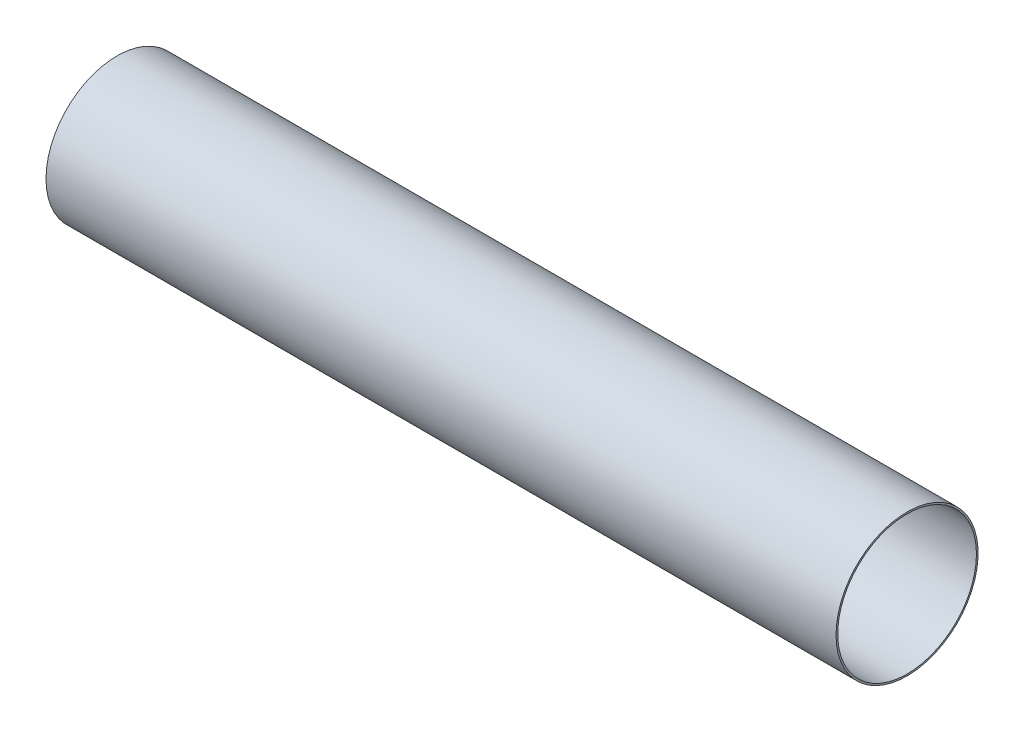
SolidWorks part; units mm, degrees
material "Thornel Mat VMA"
ref_plane "Front Plane" through (0, 0, 0) normal (0, 0, 1) x (1, 0, 0)
ref_plane "Top Plane" through (0, 0, 0) normal (0, 1, 0) x (1, 0, 0)
ref_plane "Right Plane" through (0, 0, 0) normal (1, 0, 0) x (0, 0, -1)
sketch "Sketch1" plane through (0, 0, 0) normal (1, 0, 0) x (0, 0, -1)
  circle A0 centre (0, 0) radius 84.55
  dimension "D1" = 169.1
extrude "Boss-Extrude2" add sketch "Sketch1" along normal blind 940 contours A0
sketch "Sketch3" plane through (940, 0, 0) normal (1, 0, 0) x (0, 0, -1)
  circle A0 centre (0, 0) radius 82.55
  dimension "D1" = 165.1
extrude "Cut-Extrude1" cut sketch "Sketch3" against normal blind 940
